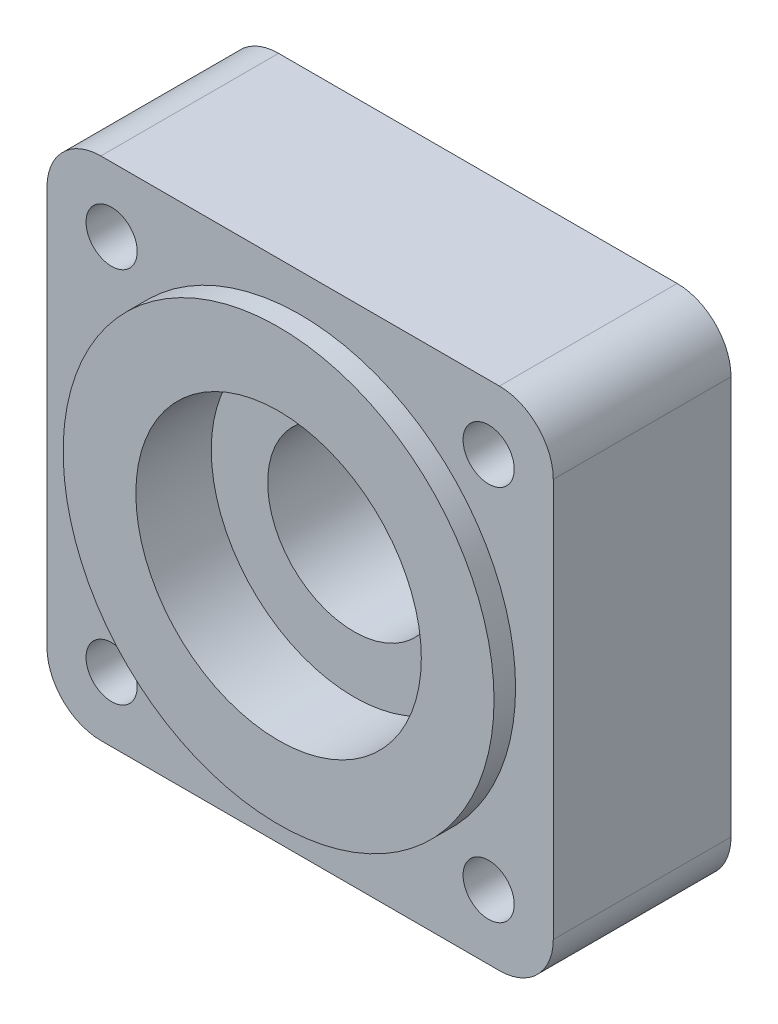
SolidWorks part; units mm, degrees
ref_plane "Front Plane" through (0, 0, 0) normal (0, 0, 1) x (1, 0, 0)
ref_plane "Top Plane" through (0, 0, 0) normal (0, 1, 0) x (1, 0, 0)
ref_plane "Right Plane" through (0, 0, 0) normal (1, 0, 0) x (0, 0, -1)
sketch "Sketch2" plane through (0, 0, 0) normal (0, 0, 1) x (1, 0, 0)
  line L1 (-67.7353, 44.9265) -> (26.2647, 44.9265)
  line L2 (-67.7353, 44.9265) -> (-67.7353, -49.0735)
  line L3 (-67.7353, -49.0735) -> (26.2647, -49.0735)
  line L4 (26.2647, 44.9265) -> (26.2647, -49.0735)
  dimension "D1" = 94
  dimension "D2" = 94
extrude "Boss-Extrude1" add sketch "Sketch2" along normal blind 33
sketch "Sketch3" plane through (0, 0, 0) normal (0, 0, 1) x (1, 0, 0)
  line L0 (-20.7353, 44.9265) -> (-20.7353, -49.0735) construction
  line L1 (26.2647, 44.9265) -> (-67.7353, 44.9265) construction
  line L2 (-67.7353, -49.0735) -> (26.2647, -49.0735) construction
  line L3 (-67.7353, -2.0735) -> (26.2647, -2.0735) construction
  line L4 (-67.7353, 44.9265) -> (-67.7353, -49.0735) construction
  line L5 (26.2647, -49.0735) -> (26.2647, 44.9265) construction
  circle A0 centre (-20.7353, -2.0735) radius 23.5
  dimension "D1" = 47
extrude "Boss-Extrude2" add sketch "Sketch3" against normal blind 21 separate body
sketch "Sketch5" plane through (0, 0, 0) normal (0, 0, 1) x (1, 0, 0)
  line L0 (-20.7353, 44.9265) -> (-20.7353, -49.0735) construction
  line L1 (26.2647, 44.9265) -> (-67.7353, 44.9265) construction
  line L2 (-67.7353, -49.0735) -> (26.2647, -49.0735) construction
  circle A0 centre (-20.7353, -2.0735) radius 15
  dimension "D1" = 30
extrude "Cut-Extrude1" cut sketch "Sketch5" against normal through all both and the other way through all
ref_plane "Plane1" through (0, 0, 33) normal (0, 0, 1) x (1, 0, 0)
sketch "Sketch6" plane through (0, 0, 33) normal (0, 0, 1) x (1, 0, 0)
  circle A0 centre (-20.7353, -2.0735) radius 26.5
  dimension "D1" = 53
sketch "Sketch7" plane through (0, 0, 33) normal (0, 0, 1) x (1, 0, 0)
  circle A0 centre (-20.7353, -2.0735) radius 40
  dimension "D1" = 80
extrude "Boss-Extrude3" add sketch "Sketch7" along normal blind 4
extrude "Cut-Extrude3" cut sketch "Sketch6" against normal blind 10 and the other way through all
sketch "Sketch8" plane through (0, 0, 0) normal (0, 0, 1) x (1, 0, 0)
  line L0 (-67.7353, -2.0735) -> (-67.7353, -0.0735)
  line L1 (26.2647, 44.9265) -> (-67.7353, 44.9265) construction
  line L3 (-18.7353, 44.9265) -> (-18.7353, 21.3412)
  line L4 (-22.7353, 44.9265) -> (-22.7353, 21.3412)
  line L5 (-18.7353, 44.9265) -> (-22.7353, 44.9265)
  line L7 (-22.7353, -49.0735) -> (-22.7353, -25.2306)
  line L8 (-18.7353, -49.0735) -> (-22.7353, -49.0735)
  line L9 (-18.7353, -49.0735) -> (-18.7353, -25.2306)
  line L10 (-67.7353, 44.9265) -> (-67.7353, -49.0735) construction
  line L11 (-20.7353, -2.0735) -> (-67.7353, -2.0735) construction
  line L12 (-67.7353, -2.0735) -> (-67.7353, -4.0735)
  line L13 (-67.7353, -0.0735) -> (-44.15, -0.0735)
  line L14 (-67.7353, -4.0735) -> (-44.15, -4.0735)
  line L15 (-20.7353, -2.0735) -> (-20.7353, 21.4265) construction
  line L16 (26.2647, -2.0735) -> (26.2647, -4.0735)
  line L17 (26.2647, -4.0735) -> (2.6794, -4.0735)
  line L18 (26.2647, -2.0735) -> (26.2647, -0.0735)
  line L19 (26.2647, -0.0735) -> (2.6794, -0.0735)
  circle A3 centre (-20.7353, -2.0735) radius 23.5 construction
  circle A4 centre (-20.7353, -2.0735) radius 23.5
  point P28 (-20.7353, 44.9265)
  point P29 (-20.7353, -49.0735)
  dimension "D2" = 2
  dimension "D3" = 2
  dimension "D1" = 2
  dimension "D4" = 2
sketch "Sketch11" plane through (0, 0, 0) normal (0, 0, 1) x (1, 0, 0)
  line L0 (26.2647, -49.0735) -> (26.2647, 44.9265) construction
  line L1 (-18.7353, 44.9265) -> (-22.7353, 44.9265) construction
  line L2 (-67.7353, -49.0735) -> (26.2647, -49.0735) construction
  circle A0 centre (14.2647, 32.9265) radius 6.5
  circle A1 centre (14.2647, -37.0735) radius 6.5
  circle A2 centre (14.2647, -37.0735) radius 6.5
  circle A3 centre (-55.7353, -37.0735) radius 6.5
  circle A4 centre (-55.7353, 32.9265) radius 6.5
  point P6 (-20.7353, 44.9265)
  point P20 (-20.7353, -2.0735)
  dimension "D2" = 13
  dimension "D5" = 13
  dimension "D8" = 4
  dimension "D1" = 12
  dimension "D3" = 35
  dimension "D4" = 70
  dimension "D6" = 12
  dimension "D7" = 12
sketch "Sketch10" plane through (0, 0, 0) normal (0, 0, 1) x (1, 0, 0)
  line L0 (-18.7353, 21.3412) -> (-18.7353, 41.9265)
  line L1 (2.6794, -0.0735) -> (23.2647, -0.0735)
  line L2 (-18.7353, 44.9265) -> (-18.7353, 21.3412) construction
  line L3 (26.2647, -0.0735) -> (2.6794, -0.0735) construction
  line L4 (23.2647, -0.0735) -> (23.2647, 24.9265)
  line L5 (-18.7353, 41.9265) -> (6.2647, 41.9265)
  line L6 (26.2647, 44.9265) -> (-67.7353, 44.9265) construction
  line L7 (-20.7353, 21.4265) -> (-20.7353, -2.0735) construction
  line L8 (-20.7353, -2.0735) -> (-35.7661, -2.0735) construction
  line L11 (-20.7353, -2.0735) -> (-67.7353, -2.0735) construction
  line L12 (2.6794, -4.0735) -> (23.2647, -4.0735)
  line L14 (23.2647, -4.0735) -> (23.2647, -29.0735)
  line L15 (-18.7353, -25.4883) -> (-18.7353, -46.0735)
  line L16 (-18.7353, -46.0735) -> (6.2647, -46.0735)
  line L17 (-22.7353, 21.3412) -> (-22.7353, 41.9265)
  line L18 (-22.7353, 41.9265) -> (-47.7353, 41.9265)
  line L19 (-64.7353, -0.0735) -> (-64.7353, 24.9265)
  line L20 (-44.15, -0.0735) -> (-64.7353, -0.0735)
  line L21 (-44.15, -4.0735) -> (-64.7353, -4.0735)
  line L22 (-64.7353, -4.0735) -> (-64.7353, -29.0735)
  line L23 (-22.7353, -25.4883) -> (-22.7353, -46.0735)
  line L24 (-22.7353, -46.0735) -> (-47.7353, -46.0735)
  arc A0 (16.9529, 24.8725) -> (23.2647, 24.9265) centre (20.1362, 21.6919) cw
  arc A1 (6.2647, 41.9265) -> (6.2647, 35.9265) centre (2.9106, 38.9265) cw
  arc A2 (16.9529, 24.8725) -> (6.2647, 35.9265) centre (14.5363, 33.2302) cw
  arc A3 (6.2647, -46.0735) -> (6.2647, -40.0735) centre (2.9106, -43.0735) ccw
  circle A4 centre (-20.7353, -2.0735) radius 23.5 construction
  arc A5 (16.9529, -29.0196) -> (6.2647, -40.0735) centre (14.5363, -37.3772) ccw
  arc A6 (16.9529, -29.0196) -> (23.2647, -29.0735) centre (20.1362, -25.8389) ccw
  arc A7 (-58.4235, -29.0196) -> (-64.7353, -29.0735) centre (-61.6068, -25.8389) cw
  arc A8 (-47.7353, 41.9265) -> (-47.7353, 35.9265) centre (-44.3812, 38.9265) ccw
  arc A9 (-58.4235, 24.8725) -> (-64.7353, 24.9265) centre (-61.6068, 21.6919) ccw
  arc A10 (-58.4235, 24.8725) -> (-47.7353, 35.9265) centre (-56.0069, 33.2302) ccw
  arc A11 (-47.7353, -46.0735) -> (-47.7353, -40.0735) centre (-44.3812, -43.0735) cw
  arc A12 (-58.4235, -29.0196) -> (-47.7353, -40.0735) centre (-56.0069, -37.3772) cw
  circle A13 centre (-20.7353, -2.0735) radius 23.5
  point P15 (23.2647, 44.9265)
  dimension "D3" = 12
  dimension "D4" = 33
  dimension "D10" = 8.7
  dimension "D1" = 3
  dimension "D2" = 3
  dimension "D5" = 25
  dimension "D6" = 25
extrude "Cut-Extrude4" cut sketch "Sketch10" along normal blind 7.5 contours A13 L1 L4 A0 A2 A1 L5 L0 | A13 L17 L18 A8 A10 A9 L19 L20 | A13 L21 L22 A7 A12 A11 L24 L23 | A13 L15 L16 A3 A5 A6 L14 L12 region at (2.8905, 21.543, 0) region at (-44.3611, 21.543, 0) region at (2.8905, -25.69, 0) region at (-44.3611, -25.69, 0)
ref_plane "Plane2" through (-18.7353, 0, 0) normal (1, 0, 0) x (0, 0, -1)
sketch "Sketch12" plane through (-18.7353, 0, 0) normal (1, 0, 0) x (0, 0, -1)
  line L0 (-3.75, 41.9265) -> (0, 41.9265) construction
  line L1 (-7.5, 41.9265) -> (0, 41.9265) construction
  line L2 (0, 41.9265) -> (0, 34.5827) construction
  line L3 (0, 21.3412) -> (0, 41.9265) construction
  line L4 (0, 21.3412) -> (0, 34.5827) construction
  line L5 (0, 21.3412) -> (-7.5, 21.3412) construction
  line L6 (-7.5, 21.3412) -> (-7.5, 41.9265) construction
  line L7 (-7.5, 41.9265) -> (-3.75, 41.9265) construction
  line L8 (-2.3946, 41.9265) -> (0, 21.3412)
  line L9 (-2.3946, 41.9265) -> (0, 41.9265)
  line L10 (0, 41.9265) -> (0, 21.3412)
  line L11 (-7.5, -2.0735) -> (10.9159, -2.0735) construction
  line L12 (-7.5, 41.9265) -> (-7.5, -46.0735) construction
  line L13 (-7.5, -46.0735) -> (-3.75, -46.0735) construction
  line L14 (0, -25.4883) -> (0, -38.7298) construction
  line L15 (0, -46.0735) -> (0, -38.7298) construction
  line L16 (-3.75, -46.0735) -> (0, -46.0735) construction
  line L17 (0, -46.0735) -> (0, -25.4883)
  line L18 (-2.3946, -46.0735) -> (0, -46.0735)
  line L19 (-2.3946, -46.0735) -> (0, -25.4883)
  dimension "D1" = 20.7241
extrude "Cut-Extrude6" cut sketch "Sketch12" against normal blind 4
ref_plane "Plane3" through (0, -0.0735, 0) normal (0, 1, 0) x (1, 0, 0)
sketch "Sketch13" plane through (0, -0.0735, 0) normal (0, 1, 0) x (1, 0, 0)
  line L0 (-64.7353, -4.78) -> (-64.7353, 0) construction
  line L3 (-64.7353, -7.5) -> (-64.7353, 0) construction
  line L4 (-67.7353, 0) -> (-44.15, 0) construction
  line L5 (-64.7353, 0) -> (-44.15, 0) construction
  line L6 (-64.7353, -2.39) -> (-44.15, 0)
  line L7 (-64.7353, -2.39) -> (-64.7353, 0)
  line L8 (-64.7353, 0) -> (-44.15, 0)
  line L9 (-64.7353, -7.5) -> (23.2647, -7.5) construction
  line L10 (-20.7353, -7.5) -> (-20.7353, 41.4234) construction
  line L11 (23.2647, 0) -> (2.6794, 0) construction
  line L12 (23.2647, -4.78) -> (23.2647, 0) construction
  line L13 (23.2647, 0) -> (2.6794, 0)
  line L14 (23.2647, -2.39) -> (23.2647, 0)
  line L15 (23.2647, -2.39) -> (2.6794, 0)
  line L16 (23.2647, -2.39) -> (23.2647, 0)
  line L17 (-64.7353, 0) -> (-44.15, 0)
  line L18 (2.6794, 0) -> (23.2647, 0)
  dimension "D1" = 2.39
extrude "Cut-Extrude7" cut sketch "Sketch13" against normal blind 4 contours L15 L14 L13 | L8 L7 L6 region at (-57.8735, -0.0735, 0.7967) region at (16.403, -0.0735, 0.7967)
extrude "Cut-Extrude8" cut sketch "Sketch11" along normal blind 26 contours A0 | A4 | A1 | A3 region at (14.2647, 32.9265, 0) region at (14.2647, -37.0735, 0) region at (-55.7353, 32.9265, 0)
sketch "Sketch14" plane through (0, 0, 0) normal (0, 0, 1) x (1, 0, 0)
  circle A0 centre (-55.7353, 32.9265) radius 4.75
  circle A1 centre (14.2647, 32.9265) radius 4.75
  circle A2 centre (14.2647, -37.0735) radius 4.75
  circle A3 centre (-55.7353, -37.0735) radius 4.75
  point P12 (-20.7353, -2.0735)
  dimension "D1" = 9.5
  dimension "D2" = 4
extrude "Cut-Extrude9" cut sketch "Sketch14" along normal through all
fillet "Fillet4" radius 10 4 edges at (26.2647, -49.0735, 16.5) (-67.7353, -49.0735, 16.5) (-67.7353, 44.9265, 16.5) (26.2647, 44.9265, 16.5)
fillet "Fillet7" radius 10 1 edges at (23.2647, -0.0735, 4.945)
fillet "Fillet8" radius 10 1 edges at (23.2647, -4.0735, 4.945)
fillet "Fillet9" radius 10 2 edges at (-64.7353, -4.0735, 4.945) (-64.7353, -0.0735, 4.945)
fillet "Fillet10" radius 10 2 edges at (-18.7353, 41.9265, 4.9473) (-22.7353, 41.9265, 4.9473)
fillet "Fillet11" radius 10 2 edges at (-22.7353, -46.0735, 4.9473) (-18.7353, -46.0735, 4.9473)
fillet "Fillet12" radius 10 1 edges at (-20.7353, -46.0735, 2.3946)
fillet "Fillet13" radius 10 3 edges at (-20.7353, 41.9265, 2.3946) (-64.7353, -2.0735, 2.39) (23.2647, -2.0735, 2.39)
ref_plane "Plane5" through (0, -2.0735, 0) normal (0, 1, 0) x (1, 0, 0)
sketch "Sketch22" plane through (0, -2.0735, 0) normal (0, 1, 0) x (1, 0, 0)
  line L0 (-20.764, 26.0616) -> (-20.764, -40.2384)
  line L1 (-20.764, 26.0616) -> (-2.764, 26.0616)
  line L2 (-2.7078, 16.1068) -> (-1.7602, 15.1592)
  line L3 (-2.764, 9.0842) -> (-4.764, 9.0842)
  line L4 (-4.764, 9.0842) -> (-4.764, -27.9158)
  line L5 (-2.7078, 16.1068) -> (-2.764, 26.0616)
  line L6 (-2.764, 9.0842) -> (-2.764, 11.6516)
  line L7 (-2.764, 11.6516) -> (-1.9905, 12.4251)
  line L8 (-4.764, -27.9158) -> (-2.764, -27.9158)
  line L9 (-2.764, -27.9158) -> (-2.764, -44.3358)
  line L10 (-20.764, -40.2384) -> (-15.874, -40.2384)
  line L11 (-15.874, -40.2384) -> (-15.874, -44.3358)
  line L12 (-15.874, -44.3358) -> (-2.764, -44.3358)
  arc A0 (-1.9905, 12.4251) -> (-1.7602, 15.1592) centre (-3.3034, 13.9124) ccw
  dimension "D1" = 18
  dimension "D3" = 37
  dimension "D4" = 2
  dimension "D5" = 16.42
  dimension "D6" = 66.3
  dimension "D7" = 4.89
revolve "Cut-Revolve2" cut sketch "Sketch22" angle 360 about L0
